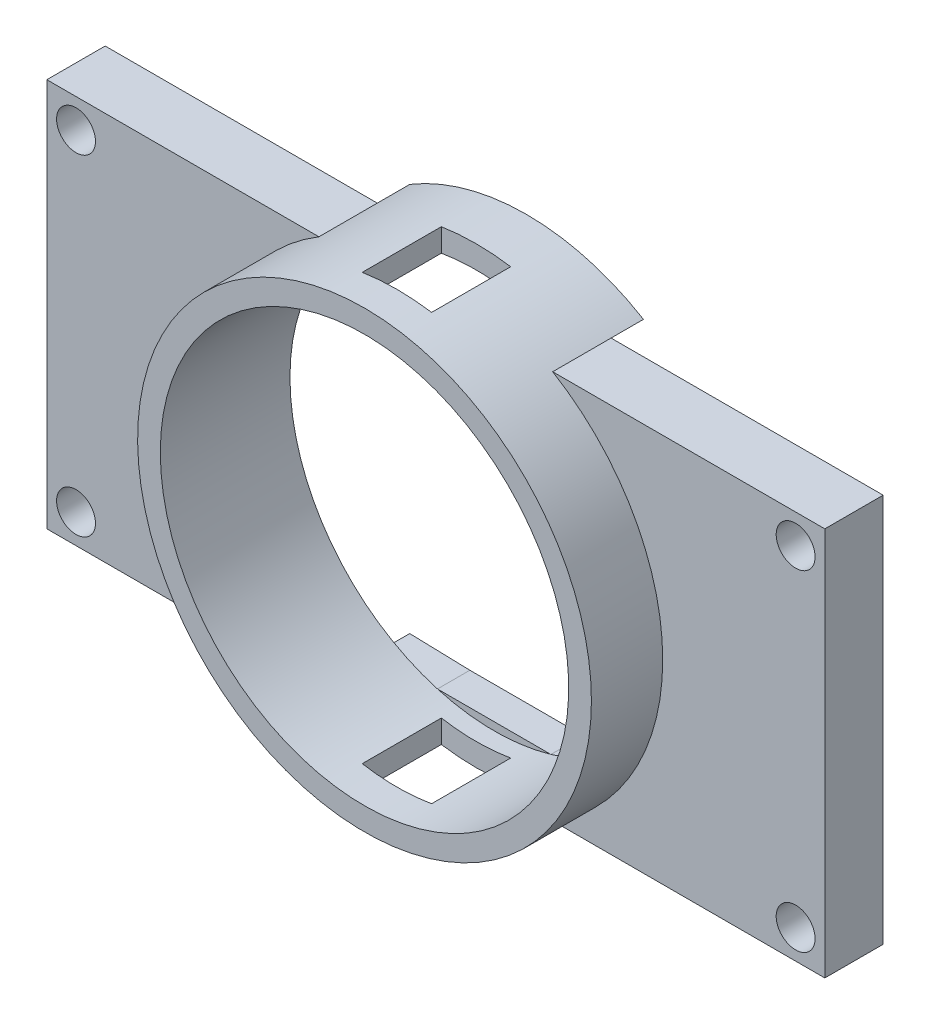
SolidWorks part; units mm, degrees
ref_plane "Front Plane" through (0, 0, 0) normal (0, 0, 1) x (1, 0, 0)
ref_plane "Top Plane" through (0, 0, 0) normal (0, 1, 0) x (1, 0, 0)
ref_plane "Right Plane" through (0, 0, 0) normal (1, 0, 0) x (0, 0, -1)
sketch "Sketch1" plane through (0, 0, 0) normal (0, 0, 1) x (1, 0, 0)
  line L0 (-16.1277, 33.5503) -> (-16.1229, 33.5503)
  line L1 (-58.1, 33.5503) -> (-16.1277, 33.5503)
  line L2 (-58.1, 33.5503) -> (-58.1, -26.4497)
  line L4 (61.9, 33.5503) -> (61.9, -26.4497)
  line L5 (61.9, 33.5503) -> (19.9278, 33.5503)
  line L6 (-58.1, -26.4497) -> (-16.1277, -26.4497)
  line L7 (61.9, -26.4497) -> (19.9278, -26.4497)
  circle A0 centre (1.9, 3.5503) radius 35
  circle A1 centre (1.9, 3.5503) radius 33.5
  circle A2 centre (-53.6, -21.9497) radius 3
  circle A3 centre (-53.6, 29.0503) radius 3
  circle A4 centre (57.4, 29.0503) radius 3
  circle A5 centre (57.4, -21.9497) radius 3
  circle A6 centre (-53.6, 29.0503) radius 1.5
  circle A7 centre (57.4, 29.0503) radius 1.5
  circle A9 centre (57.4, -21.9497) radius 1.5
  circle A10 centre (-53.6, -21.9497) radius 1.5
  point P7 (-58.1, 3.5503)
  point P8 (1.9, 3.5503)
  dimension "D3" = 70
  dimension "D4" = 67
  dimension "D5" = 3
  dimension "D6" = 6
  dimension "D1" = 120
  dimension "D2" = 60
  dimension "D9" = 4.5
  dimension "D10" = 4.5
extrude "Boss-Extrude1" add sketch "Sketch1" along normal blind 20 contours A0 A1 region at (1.9, 37.5604, 0)
extrude "Boss-Extrude3" add sketch "Sketch1<5>" along normal blind 4 contours A4 A7 | A3 A6 | A2 A10 | A5 A9 region at (-56.5151, -21.9497, 0) region at (-56.5151, 29.0503, 0) region at (54.4849, 29.0503, 0) region at (54.4849, -21.9497, 0)
sketch "Sketch1<5>" plane through (0, 0, 0) normal (0, 0, 1) x (1, 0, 0) same geometry as "Sketch1"
extrude "Boss-Extrude4" add sketch "Sketch1<6>" along normal blind 9 contours A0 L1 L2 L6 A3 A2 | A0 L7 L4 L5 A5 A4 region at (-42.3854, 3.5503, 0) region at (46.1855, 3.5503, 0)
sketch "Sketch1<6>" plane through (0, 0, 0) normal (0, 0, 1) x (1, 0, 0) same geometry as "Sketch1"
ref_plane "Plane1" through (0, -26.4497, 0) normal (0, -1, 0) x (-1, 0, 0)
sketch "Sketch3" plane through (0, -26.4497, 0) normal (0, -1, 0) x (-1, 0, 0)
  line L0 (-1.9, -20) -> (-1.9, 0) construction
  line L1 (-36.9, -20) -> (33.1, -20) construction
  line L2 (16.1277, 0) -> (-19.9278, 0) construction
  line L3 (3.45, -15) -> (-7.25, -15)
  line L8 (-7.25, -15) -> (-7.25, -2.8)
  line L9 (-7.25, -2.8) -> (3.45, -2.8)
  line L10 (3.45, -2.8) -> (3.45, -15)
  point P10 (-1.9, -15)
  dimension "D1" = 5
  dimension "D2" = 10.7
  dimension "D3" = 12.2
extrude "Cut-Extrude2" cut sketch "Sketch3" against normal blind 76 and the other way blind 22
ref_plane "Plane2" through (0, 0, 0) normal (0, 0, -1) x (-1, 0, 0)
sketch "Sketch5" plane through (0, 0, 0) normal (0, 0, -1) x (-1, 0, 0)
  line L0 (16.1277, -26.4497) -> (6.8475, -26.7107)
  line L1 (16.1277, 33.5503) -> (6.8475, 33.8114)
  line L2 (-19.9278, 33.5503) -> (-10.6476, 33.8114)
  line L3 (-19.9278, -26.4497) -> (-10.6476, -26.7107)
  line L4 (-10.6476, 33.8114) -> (6.8475, 33.8114)
  line L5 (-10.6476, -26.7107) -> (6.8475, -26.7107)
  circle A1 centre (-1.9, 3.5503) radius 35
  circle A2 centre (-1.9, 3.5503) radius 31.5
extrude "Boss-Extrude9" add sketch "Sketch5" against normal blind 20 contours A2 A1 | A2 A1 | A2 A1 | A2 A1 region at (1.9, -28.7756, 0) region at (-11.4691, -25.9208, 0) region at (36.2403, 3.5503, 0) region at (1.9, 35.8762, 0)
extrude "Boss-Extrude11" add sketch "Sketch5<11>" along normal blind 5 contours A2 L1 A1 L2 | L4 A2 | L5 A2 | A2 L3 A1 L0 region at (1.9, -28.7756, 0) region at (1.9, -27.2072, 0) region at (1.9, 35.8762, 0) region at (1.9, 34.3078, 0)
sketch "Sketch5<11>" plane through (0, 0, 0) normal (0, 0, -1) x (-1, 0, 0) same geometry as "Sketch5"
extrude "Cut-Extrude3" cut sketch "Sketch3<2>" against normal blind 92 and the other way blind 22
sketch "Sketch3<2>" plane through (0, -26.4497, 0) normal (0, -1, 0) x (-1, 0, 0) same geometry as "Sketch3"
